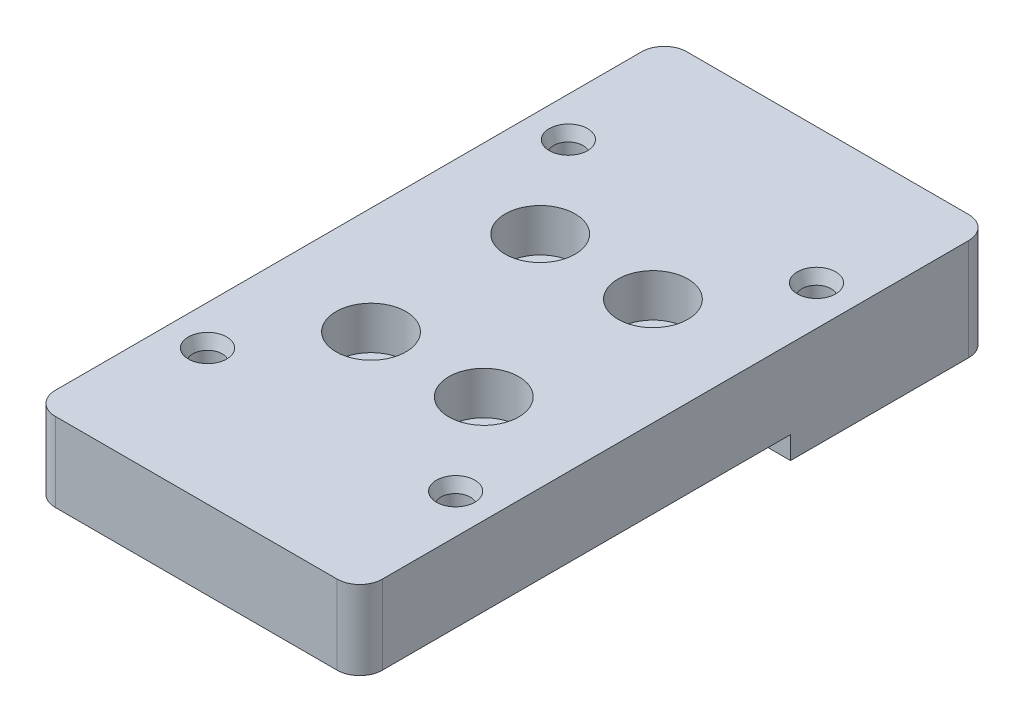
SolidWorks part; units mm, degrees
ref_plane "前视基准面" through (0, 0, 0) normal (0, 0, 1) x (1, 0, 0)
ref_plane "上视基准面" through (0, 0, 0) normal (0, 1, 0) x (1, 0, 0)
ref_plane "右视基准面" through (0, 0, 0) normal (1, 0, 0) x (0, 0, -1)
other "Configuration Table"
sketch "草图1" plane through (0, 0, 0) normal (0, 1, 0) x (1, 0, 0)
  line L1 (-14.5, 10.2) -> (14.5, 10.2)
  line L2 (-14.5, 10.2) -> (-14.5, -10.2)
  line L3 (-14.5, -10.2) -> (14.5, -10.2)
  line L4 (14.5, 10.2) -> (14.5, -10.2)
  line L5 (-14.5, 10.2) -> (14.5, -10.2) construction
  line L6 (-14.5, -10.2) -> (14.5, 10.2) construction
  point P0 (0, 0)
extrude "凸台-拉伸1" add sketch "草图1" against normal blind 7
sketch "草图2" plane through (0, 0, 0) normal (0, 1, 0) x (1, 0, 0)
  line L1 (-5, -7.5) -> (5, -7.5) construction
  line L2 (-5, -7.5) -> (-5, 7.5) construction
  line L3 (-5, 7.5) -> (5, 7.5) construction
  line L4 (5, -7.5) -> (5, 7.5) construction
  line L5 (-5, -7.5) -> (5, 7.5) construction
  line L6 (-5, 7.5) -> (5, -7.5) construction
  circle A0 centre (5, 7.5) radius 1.65
  circle A1 centre (5, -7.5) radius 1.65
  circle A2 centre (-5, -7.5) radius 1.65
  circle A3 centre (-5, 7.5) radius 1.65
  point P0 (0, 0)
extrude "切除-拉伸1" cut sketch "草图2" against normal up to surface (7 mm away) up to face at (0, -7, 0)
sketch "草图4" plane through (0, 0, 0) normal (0, 1, 0) x (1, 0, 0)
  line L1 (-14.5, 10.2) -> (14.5, 10.2)
  line L2 (-14.5, 10.2) -> (-14.5, 28)
  line L3 (-14.5, 28) -> (14.5, 28)
  line L4 (14.5, 10.2) -> (14.5, 28)
  line L5 (-14.5, 10.2) -> (14.5, 28) construction
  line L6 (-14.5, 28) -> (14.5, 10.2) construction
  line L7 (-14.5, -10.2) -> (14.5, -10.2)
  line L8 (-14.5, -10.2) -> (-14.5, -28)
  line L9 (-14.5, -28) -> (14.5, -28)
  line L10 (14.5, -10.2) -> (14.5, -28)
  line L11 (-14.5, -10.2) -> (14.5, -28) construction
  line L12 (-14.5, -28) -> (14.5, -10.2) construction
  point P4 (0, 19.1)
  point P10 (0, -19.1)
extrude "凸台-拉伸2" add sketch "草图4" against normal blind 9
sketch "草图3" plane through (0, 0, 0) normal (0, 1, 0) x (1, 0, 0)
  circle A0 centre (-5, 7.5) radius 3.1
  circle A1 centre (5, 7.5) radius 3.1
  circle A2 centre (5, -7.5) radius 3.1
  circle A3 centre (-5, -7.5) radius 3.1
extrude "切除-拉伸2" cut sketch "草图3" against normal blind 3.8
fillet "圆角2" radius 2 4 edges at (14.5, -4.5, -28) (-14.5, -4.5, -28) (-14.5, -4.5, 28) (14.5, -4.5, 28)
sketch "草图5" plane through (0, -9, 0) normal (0, -1, 0) x (1, 0, 0)
  circle A0 centre (0, -20) radius 8
extrude "凸台-拉伸3" add sketch "草图5" along normal blind 3
sketch "草图6" plane through (0, -12, 0) normal (0, -1, 0) x (1, 0, 0)
  circle A0 centre (0, -20) radius 5
extrude "凸台-拉伸4" add sketch "草图6" along normal blind 0.8
sketch "草图7" plane through (0, -12.8, 0) normal (0, -1, 0) x (1, 0, 0)
  circle A1 centre (0, -20) radius 1.8
extrude "切除-拉伸3" cut sketch "草图7" against normal offset from surface (9.8 mm away) 3 up to face at (-5, 0, 10.6)
sketch "草图9" plane through (0, -12.8, 0) normal (0, -1, 0) x (1, 0, 0)
  circle A0 centre (0, -20) radius 2.65
extrude "切除-拉伸5" cut sketch "草图9" against normal blind 0.4
chamfer "倒角3" distance 0.4 angle 70 1 edges at (0, -12.4, -21.8) first distance on face at (0, -12.4, -22.65)
sketch "草图8" plane through (0, 0, 0) normal (0, 1, 0) x (1, 0, 0)
  circle A0 centre (-11, 16) radius 1.3
  circle A1 centre (11, 16) radius 1.3
  circle A2 centre (-11, -16) radius 1.3
  circle A3 centre (11, -16) radius 1.3
extrude "切除-拉伸4" cut sketch "草图8" against normal up to surface (9 mm away) up to face at (0, -9, -23.1536)
fillet "圆角3" radius 1.5 1 edges at (0, -9, -28)
chamfer "倒角2" distance 0.4 angle 70 4 edges at (11, 0, 17.3) (-11, 0, 17.3) (11, 0, -14.7) (-11, 0, -14.7) first distance on face at (11, 0, -14.7)
sketch "草图10" plane through (0, -9, 0) normal (0, -1, 0) x (1, 0, 0)
  line L4 (12.5, 28) -> (-12.5, 28)
  line L5 (-14.5, 26) -> (-14.5, 10.2)
  line L6 (-14.5, 10.2) -> (14.5, 10.2)
  line L7 (14.5, 10.2) -> (14.5, 26)
  line L8 (12.5, 28) -> (-12.5, 28)
  line L9 (-14.5, 26) -> (-14.5, 10.2)
  line L10 (-14.5, 10.2) -> (14.5, 10.2)
  line L11 (14.5, 10.2) -> (14.5, 26)
  arc A2 (-12.5, 28) -> (-14.5, 26) centre (-12.5, 26) ccw
  arc A3 (14.5, 26) -> (12.5, 28) centre (12.5, 26) ccw
  arc A4 (-12.5, 28) -> (-14.5, 26) centre (-12.5, 26) ccw
  arc A5 (14.5, 26) -> (12.5, 28) centre (12.5, 26) ccw
  dimension "D1" = 0
extrude "切除-拉伸6" cut sketch "草图10" against normal up to surface (2 mm away) up to face at (-5, -7, -5.85)
